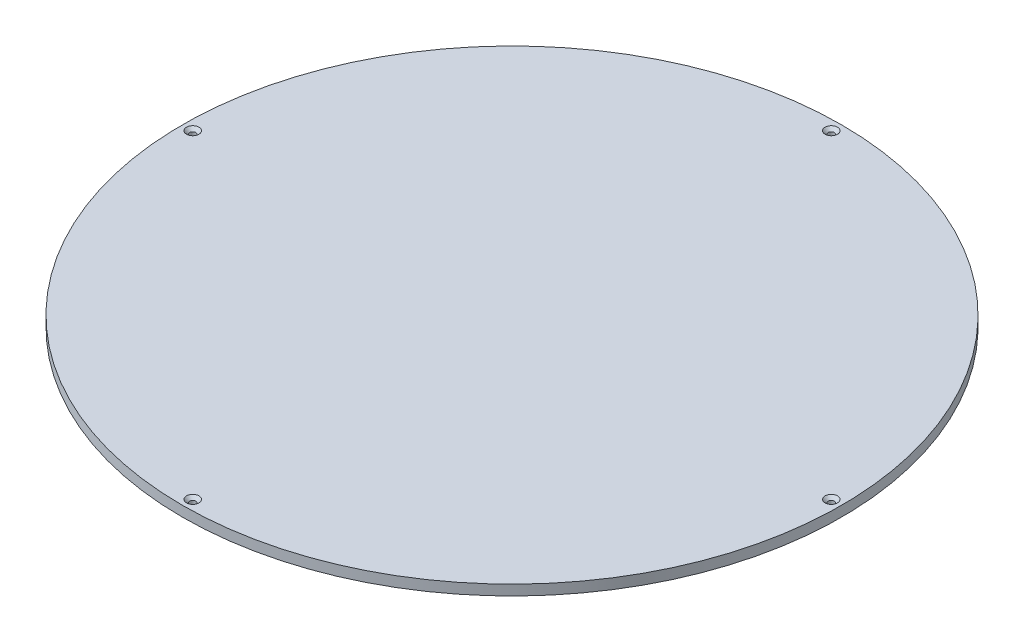
SolidWorks part; units mm, degrees
material "Pine"
ref_plane "Front Plane" through (0, 0, 0) normal (0, 0, 1) x (1, 0, 0)
ref_plane "Top Plane" through (0, 0, 0) normal (0, 1, 0) x (1, 0, 0)
ref_plane "Right Plane" through (0, 0, 0) normal (1, 0, 0) x (0, 0, -1)
sketch "Sketch1" plane through (0, 0, 0) normal (0, 1, 0) x (1, 0, 0)
  line L0 (-8.7941, 0) -> (197.1788, 0) construction
  circle A0 centre (0, 0) radius 160
  circle A1 centre (155, 0) radius 1.5
  circle A2 centre (0, -155) radius 1.5
  circle A3 centre (-155, 0) radius 1.5
  circle A4 centre (0, 155) radius 1.5
  point P16 (0, 0)
  dimension "D1" = 320
  dimension "D2" = 3
  dimension "D3" = 155
  dimension "D4" = 4
extrude "Boss-Extrude1" add sketch "Sketch1" against normal blind 5
chamfer "Chamfer1" distance 1.5 angle 45 4 edges at (155, 0, 1.5) (-155, 0, 1.5) (0, 0, -153.5) (0, 0, 156.5)
equation "\"rod_diameter\"= 8"
equation "\"rod_hole_thickness\"= 4"
equation "\"rod_radius\"= \"rod_diameter\" / 2"
equation "\"platter_diameter\"= 320"
equation "\"platter_radius\"= \"platter_diameter\" / 2"
equation "\"extruder_mount_hole_spacing\"= 50"
equation "\"arm_rod_spacing\"= 40"
equation "\"top_frame_rod_spacing\"= \"arm_rod_spacing\" + 40"
equation "\"motor_level_rod_spacing\"= 15"
equation "\"linear_bearing_diameter\"= 15"
equation "\"z_rod_spacing\"= 75"
equation "\"platter_rod_spacing\"= 50"
equation "\"rod_nut_thickness\"= 6.5"
equation "\"rod_nut_inscribed_diameter\"= 13"
equation "\"z_height\"= 350"
equation "\"D1@Sketch1\"=\"platter_diameter\""
equation "\"D3@Sketch1\"=\"platter_radius\"-5"
